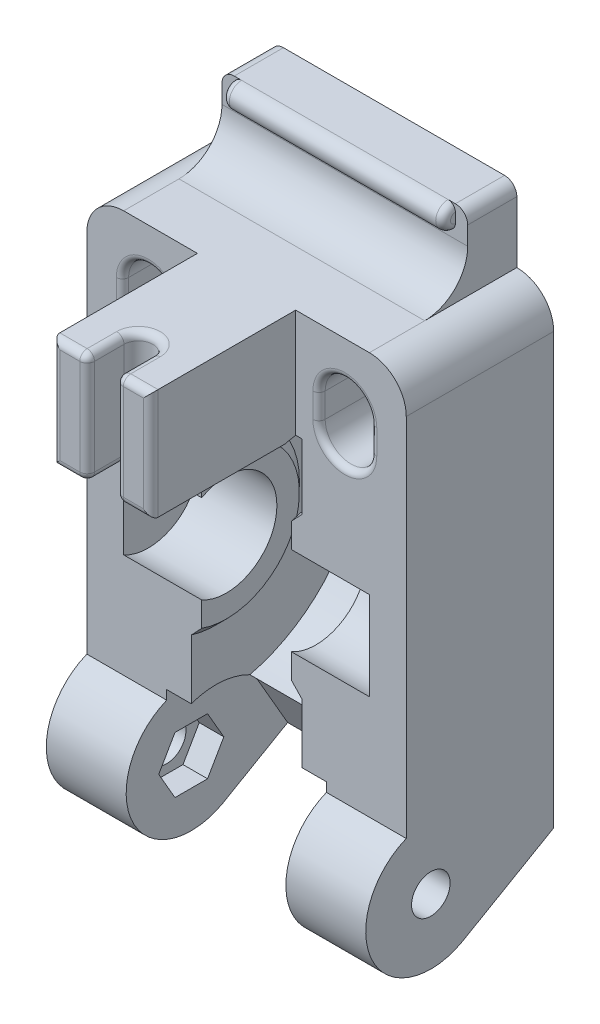
SolidWorks part; units mm, degrees
ref_plane "Front Plane" through (0, 0, 0) normal (0, 0, 1) x (1, 0, 0)
ref_plane "Top Plane" through (0, 0, 0) normal (0, 1, 0) x (1, 0, 0)
ref_plane "Right Plane" through (0, 0, 0) normal (1, 0, 0) x (0, 0, -1)
sketch "Sketch1" plane through (0, 0, 0) normal (1, 0, 0) x (0, 0, -1)
  line L0 (10, -0.346) -> (2.5517, -4.6453)
  line L1 (-2, 37.654) -> (10, 37.654)
  line L2 (-2, 37.654) -> (-2, 4.9082)
  line L3 (10, -0.346) -> (-2, -0.346) construction
  line L4 (10, 37.654) -> (10, -0.346)
  line L5 (-2, -0.346) -> (-2, 4.9082) construction
  arc A0 (-2, 4.9082) -> (2.5517, -4.6453) centre (0, 0) ccw
  dimension "D1" = 5.3
  dimension "D2" = 12
  dimension "D3" = 2
  dimension "D4" = 38
  dimension "D5" = 0.346
extrude "Boss-Extrude1" add sketch "Sketch1" along normal mid plane 26
sketch "Sketch17" plane through (0, 37.654, 0) normal (0, 1, 0) x (1, 0, 0)
  line L2 (13, -2) -> (-13, -2) construction
  line L3 (-4, -2) -> (4, -2)
  line L4 (-4, -2) -> (-4, -13.8)
  line L5 (-4, -13.8) -> (-1.175, -13.8)
  line L6 (4, -2) -> (4, -13.8)
  line L7 (-4, -2) -> (4, -13.8) construction
  line L8 (-4, -13.8) -> (4, -2) construction
  line L13 (1.175, -10.8) -> (1.175, -13.8)
  line L15 (-1.175, -13.8) -> (-1.175, -10.8)
  line L16 (1.175, -13.8) -> (4, -13.8)
  arc A0 (1.175, -10.8) -> (-1.175, -10.8) centre (0, -10.8) ccw
  point P5 (0, -7.9)
  dimension "D3" = 3
  dimension "D4" = 2.35
  dimension "D1" = 11.8
  dimension "D2" = 8
extrude "Boss-Extrude7" add sketch "Sketch17" against normal blind 9
sketch "Sketch2" plane through (0, 0, 0) normal (1, 0, 0) x (0, 0, -1)
  circle A0 centre (0, 17) radius 12
  dimension "D3" = 24
  dimension "D1" = 17
extrude "Cut-Extrude1" cut sketch "Sketch2" against normal mid plane 9
sketch "Sketch4" plane through (0, 0, 0) normal (1, 0, 0) x (0, 0, -1)
  line L0 (5.1964, 2.9995) -> (7.8454, -1.5897)
  line L1 (2.5517, -4.6453) -> (10, -0.346) construction
  line L2 (2.9995, -5.1964) -> (7.8454, -2.3993)
  line L3 (7.8454, -2.3993) -> (7.8454, -1.5897)
  arc A0 (5.1964, 2.9995) -> (2.9995, -5.1964) centre (0, 0) ccw
  dimension "D1" = 12
extrude "Cut-Extrude3" cut sketch "Sketch4" against normal mid plane 13
sketch "Sketch6" plane through (0, 0, 0) normal (1, 0, 0) x (0, 0, -1)
  circle A0 centre (0, 0) radius 1.57
sketch "Sketch8" plane through (-4.5, 0, 0) normal (1, 0, 0) x (0, 0, -1)
  line L0 (-2, 23.4992) -> (-2, 10.5008)
  line L3 (-2, 37.654) -> (-2, 4.9082) construction
  arc A0 (-2, 10.5008) -> (-2, 23.4992) centre (0, 17) ccw
  arc A1 (10, 23.6332) -> (-2, 28.8322) centre (0, 17) ccw construction
  dimension "D1" = 6.8
sketch "Sketch9" plane through (4.5, 0, 0) normal (-1, 0, 0) x (0, 0, 1)
  line L0 (2, 23.4992) -> (2, 10.5008)
  arc A0 (2, 23.4992) -> (2, 10.5008) centre (0, 17) ccw
extrude "Cut-Extrude4" cut sketch "Sketch6" against normal mid plane 26
extrude "Boss-Extrude2" add sketch "Sketch8" along normal blind 0.85
extrude "Boss-Extrude3" add sketch "Sketch9" along normal blind 0.85
sketch "Sketch3" plane through (0, 0, 0) normal (1, 0, 0) x (0, 0, -1)
  circle A0 centre (0, 17) radius 4.12
  dimension "D1" = 8.24
extrude "bearing_axis" cut sketch "Sketch3" against normal mid plane 20
chamfer "Chamfer1" distance 0.85 angle 45 2 edges at (3.65, 17, -6.8) (-3.65, 17, -6.8)
sketch "Sketch12" plane through (-6.5, 0, 0) normal (1, 0, 0) x (0, 0, -1)
  line L1 (2.65, 0) -> (1.325, 2.295)
  line L2 (1.325, 2.295) -> (-1.325, 2.295)
  line L3 (-1.325, 2.295) -> (-2.65, 0)
  line L4 (-2.65, 0) -> (-1.325, -2.295)
  line L5 (-1.325, -2.295) -> (1.325, -2.295)
  line L6 (1.325, -2.295) -> (2.65, 0)
  circle A0 centre (0, 0) radius 2.295 construction
  dimension "D1" = 4.59
extrude "Cut-Extrude6" cut sketch "Sketch12" against normal blind 2
sketch "Sketch14" plane through (6.5, 0, 0) normal (-1, 0, 0) x (0, 0, 1)
  line L1 (-2.65, 0) -> (-1.325, -2.295)
  line L2 (-1.325, -2.295) -> (1.325, -2.295)
  line L3 (1.325, -2.295) -> (2.65, 0)
  line L4 (2.65, 0) -> (1.325, 2.295)
  line L5 (1.325, 2.295) -> (-1.325, 2.295)
  line L6 (-1.325, 2.295) -> (-2.65, 0)
  circle A0 centre (0, 0) radius 2.295 construction
extrude "Cut-Extrude7" cut sketch "Sketch14" against normal blind 2
sketch "Sketch15" plane through (0, 37.654, 0) normal (0, 1, 0) x (1, 0, 0)
  line L0 (13, 10) -> (-13, 10) construction
  line L2 (-10, 10) -> (-10, 6)
  line L3 (-10, 6) -> (10, 6)
  line L4 (10, 10) -> (10, 6)
  line L5 (0, 10) -> (10, 6) construction
  line L6 (-10, 6) -> (0, 10) construction
  line L7 (-10, 10) -> (10, 10)
  point P0 (0, 10)
  dimension "D1" = 4
  dimension "D2" = 20
extrude "Boss-Extrude4" add sketch "Sketch15" along normal blind 6
fillet "Fillet1" radius 3.5 1 edges at (0, 37.654, -6)
fillet "Fillet2" radius 3 2 edges at (-13, 37.654, -4) (13, 37.654, -4)
fillet "Fillet3" radius 1 2 edges at (-10, 43.654, -8) (10, 43.654, -8)
sketch "Sketch16" plane through (0, 0, 0) normal (1, 0, 0) x (0, 0, -1)
  circle A0 centre (6, 42.654) radius 1
extrude "Boss-Extrude5" add sketch "Sketch16" along normal mid plane 18
fillet "Fillet4" radius 0.6 2 edges at (9, 42.654, -5) (-9, 42.654, -5)
sketch "Sketch18" plane through (0, 0, -10) normal (0, 0, 1) x (1, 0, 0)
  line L0 (-8, 30.654) -> (-8, 32.654) construction
  line L1 (-10.1, 30.654) -> (-10.1, 32.654)
  line L2 (-5.9, 30.654) -> (-5.9, 32.654)
  line L3 (-13, -0.346) -> (-13, 34.654) construction
  line L5 (8, 32.654) -> (8, 30.654) construction
  line L6 (13, -0.346) -> (13, 34.654) construction
  line L7 (10, 37.654) -> (-10, 37.654) construction
  line L8 (10.1, 32.654) -> (10.1, 30.654)
  line L9 (5.9, 32.654) -> (5.9, 30.654)
  arc A0 (-10.1, 30.654) -> (-5.9, 30.654) centre (-8, 30.654) ccw
  arc A1 (-5.9, 32.654) -> (-10.1, 32.654) centre (-8, 32.654) ccw
  arc A2 (10.1, 32.654) -> (5.9, 32.654) centre (8, 32.654) ccw
  arc A3 (5.9, 30.654) -> (10.1, 30.654) centre (8, 30.654) ccw
  point P2 (-8, 31.654)
  point P14 (8, 31.654)
  dimension "D1" = 2.1
  dimension "D2" = 2
  dimension "D3" = 5
  dimension "D5" = 6
  dimension "D6" = 5
extrude "Cut-Extrude8" cut sketch "Sketch18" along normal up to surface (12 mm away) up to face at (6.4836, 19.1925, 2)
fillet "Fillet5" radius 0.6 14 edges at (-1.175, 28.654, 12.3) (1.175, 28.654, 12.3) (-1.175, 37.654, 12.3) (1.175, 37.654, 12.3) (0, 28.654, 9.625) (0, 37.654, 9.625) (4, 33.154, 13.8) (1.175, 33.154, 13.8) (-1.175, 33.154, 13.8) (-4, 33.154, 13.8) (2.5875, 28.654, 13.8) (-2.5875, 28.654, 13.8) (2.5875, 37.654, 13.8) (-2.5875, 37.654, 13.8)
fillet "Fillet6" radius 0.5 8 edges at (5.9, 31.654, 2) (8, 28.554, 2) (10.1, 31.654, 2) (-10.1, 31.654, 2) (-8, 28.554, 2) (-5.9, 31.654, 2) (8, 34.754, 2) (-8, 34.754, 2)
